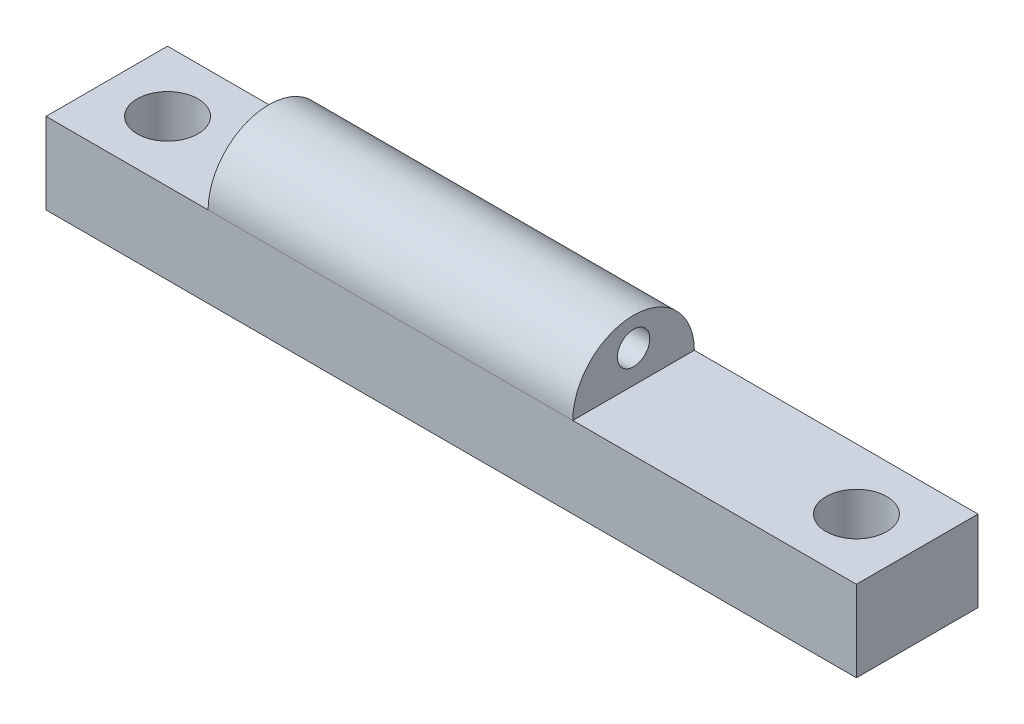
SolidWorks part; units mm, degrees
ref_plane "Front Plane" through (0, 0, 0) normal (0, 0, 1) x (1, 0, 0)
ref_plane "Top Plane" through (0, 0, 0) normal (0, 1, 0) x (1, 0, 0)
ref_plane "Right Plane" through (0, 0, 0) normal (1, 0, 0) x (0, 0, -1)
sketch "Sketch1" plane through (0, 0, 0) normal (0, 1, 0) x (1, 0, 0)
  line L1 (-25.4, 3.81) -> (25.4, 3.81)
  line L2 (-25.4, 3.81) -> (-25.4, -3.81)
  line L3 (-25.4, -3.81) -> (25.4, -3.81)
  line L4 (25.4, 3.81) -> (25.4, -3.81)
  line L5 (-25.4, 3.81) -> (25.4, -3.81) construction
  line L6 (-25.4, -3.81) -> (25.4, 3.81) construction
  point P0 (0, 0)
  dimension "D1" = 50.8
  dimension "D2" = 7.62
extrude "Boss-Extrude1" add sketch "Sketch1" along normal blind 5.08
sketch "Sketch2" plane through (25.4, 0, 0) normal (1, 0, 0) x (0, 0, -1)
  line L0 (-3.81, 5.08) -> (3.81, 5.08) construction
  line L5 (-3.81, 0) -> (3.81, 0)
  line L6 (3.81, 0) -> (3.81, 5.08)
  line L7 (3.81, 5.08) -> (-3.81, 5.08)
  line L8 (-3.81, 5.08) -> (-3.81, 0)
  line L11 (3.81, 5.08) -> (-3.81, 5.08)
  arc A0 (-3.81, 5.08) -> (3.81, 5.08) centre (0, 5.08) cw
  circle A1 centre (0, 7.112) radius 1.016
  dimension "D3" = 2.032
  dimension "D2" = 2.032
  dimension "D1" = 0
extrude "Boss-Extrude2" add sketch "Sketch2" against normal blind 22.86 from offset 17.78 offset against normal yes
sketch "Sketch3" plane through (0, 5.08, 0) normal (0, 1, 0) x (1, 0, 0)
  line L0 (-25.4, 3.81) -> (-25.4, -3.81) construction
  line L1 (25.4, -3.81) -> (25.4, 3.81) construction
  circle A0 centre (-21.59, 0) radius 1.905
  circle A1 centre (21.59, 0) radius 1.905
  dimension "D1" = 3.81
  dimension "D2" = 3.81
  dimension "D3" = 3.81
extrude "Cut-Extrude1" cut sketch "Sketch3" against normal through all
